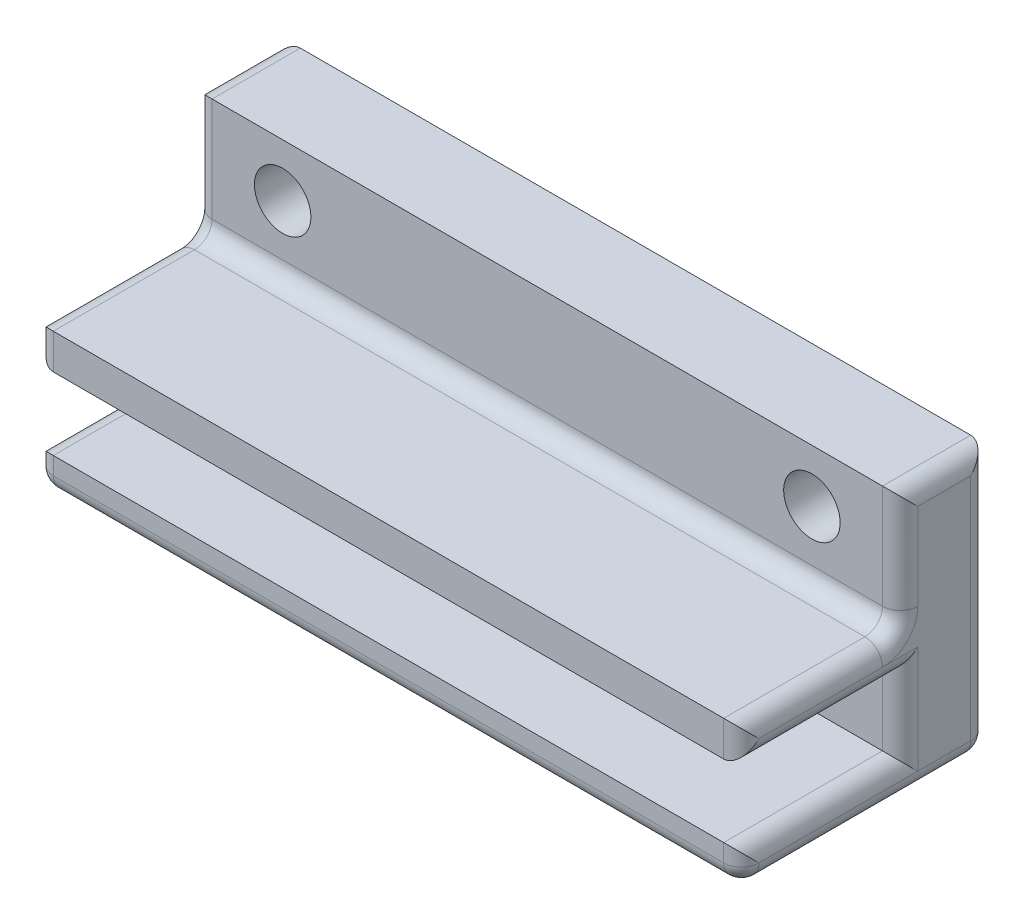
SolidWorks part; units mm, degrees
note: The reader was unsure of these and kept them because the rebuilt part matched: shared geometry of "Sketch2<3>".
material "PETG"
ref_plane "Front Plane" through (0, 0, 0) normal (0, 0, 1) x (1, 0, 0)
ref_plane "Top Plane" through (0, 0, 0) normal (0, 1, 0) x (1, 0, 0)
ref_plane "Right Plane" through (0, 0, 0) normal (1, 0, 0) x (0, 0, -1)
sketch "Sketch2" plane through (0, 0, 0) normal (0, 0, 1) x (1, 0, 0)
  line L0 (0, 7.5) -> (0, -7.5) construction
  line L1 (-20, -7.5) -> (20, -7.5)
  line L2 (-20, -7.5) -> (-20, 7.5)
  line L3 (-20, 7.5) -> (20, 7.5)
  line L4 (20, -7.5) -> (20, 7.5)
  line L5 (-20, -7.5) -> (20, 7.5) construction
  line L6 (-20, 7.5) -> (20, -7.5) construction
  line L7 (-20, 4.5) -> (20, 4.5) construction
  line L8 (-20, 0.6) -> (20, 0.6)
  line L9 (-20, -1.4) -> (20, -1.4)
  line L10 (-20, -5.5) -> (20, -5.5)
  circle A0 centre (-15, 4.5) radius 1.6
  circle A1 centre (15, 4.5) radius 1.6
  point P0 (0, 0)
  dimension "D1" = 3.2
  dimension "D2" = 30
  dimension "D3" = 40
  dimension "D4" = 3
  dimension "D5" = 15
  dimension "D6" = 4.1
  dimension "D7" = 2
  dimension "D8" = 2
extrude "Boss-Extrude1" add sketch "Sketch2" along normal blind 5 contours L2 L8 L4 L3 A0 A1 | L2 L9 L4 L8 | L2 L10 L4 L9 | L10 L2 L1 L4
extrude "Boss-Extrude2" add sketch "Sketch2<3>" along normal blind 14 contours L2 L9 L4 L8 | L10 L2 L1 L4
sketch "Sketch2<3>" plane through (0, 0, 0) normal (0, 0, 1) x (1, 0, 0) same geometry as "Sketch2"
fillet "Fillet1" radius 1 21 edges at (0, -7.5, 14) (0, -7.5, 0) (-20, 4.05, 5) (-20, 0.6, 9.5) (-20, -0.4, 14) (-20, -1.4, 9.5) (-20, -5.5, 9.5) (-20, -6.5, 14) (-20, -7.5, 7) (-20, 0, 0) (-20, 7.5, 2.5) (20, -1.4, 9.5) (20, -0.4, 14) (20, 0.6, 9.5) (20, 4.05, 5) (20, 7.5, 2.5) (20, 0, 0) (20, -7.5, 7) (20, -6.5, 14) (20, -5.5, 9.5) (0, 0.6, 5)
equation "\"DTailTube\"= 16mm'Диаметр трубки хвостового оперения"
equation "\"FusLenght\"= 700mm"
equation "\"DMotor\"= 35.2mm"
equation "\"MotorArm\"= 320mm"
equation "\"DFus\"= 150mm"
equation "\"DFusTube\"= 30mm'Диаметр трубки внутри фюзеляжа"
equation "\"FusTubeHeight\"= 40mm"
equation "\"FusCentralPartLenght\"= 410mm"
equation "\"FusNoseLenght\"= 150mm"
equation "\"WingOffset\"= 1mm'Расстояние от внутренней поверхности фюзеляжа до профиля крыла по вертикали"
equation "\"EllipseRatio\"= 0.95'Центральная часть фюзеляжа - эллипс. Этот параметр - отношение длин осей эллипса"
equation "\"FrameOffset\"= 0.6mm"
equation "\"DThreadedInsert\"= 3mm'Внешний диамер резьбовых втулок"
equation "\"ThreadedInsertLenght\"=4mm'Длина резьбовых втулок"
equation "\"ThreadedInsertThread\"=2mm'Диаметр резьбы втулки"
equation "\"CenterSectionLenght\"= 140mm'Длина центроплана"
equation "\"b\"= 1700mm'Размах"
equation "\"cwr\"= 236mm'Корневая хорда крыла"
equation "\"TR\"= 0.75'Сужение крыла"
equation "\"cwt\"= \"TR\" * \"cwr\"'Концевая хорда крыла"
equation "\"DWingMainSpar\"= 16mm'Диаметр главного лонжерона крыла"
equation "\"DWingSecondSpar\"= 8mm'Диаметр второго лонжерона крыла"
equation "\"WingSparsDistance\"= 80mm'Расстояния между отверстиями по лонжерон крыла"
equation "\"c\"= 210mm'САХ крыла"
equation "\"FusTubeLenght\"= \"FusLenght\"-50mm'Длина трубки фюзеляжа"
equation "\"bt\"=291mm'Высота лопатки хвоста"
equation "\"ct\"=182mm'Корневая хорда хвоста"
equation "\"lambda_t\"=0.3'Доля хвоста, занатая рулем высоты"
equation "\"TailTubeLenght\"=730mm'Длина хвостовой балки"
equation "\"DStringer\"=6mm'Диаметр стрингеров"
equation "\"TailConnectorBaseLenght\"=20mm'Высота основания конектора хвоста"
equation "\"CargoHolderHoleDistance\"=30mm'Расстояние между крепежными отверстиями для держателя груза"
equation "\"FuselageThickness\"=1.2mm'Толщина фюзеляжа"
equation "\"DTailSpar\"=6mm'Диаметр лонжерона хвостового оперения"
equation "\"TailSparDistance\"=40mm'Расстояние между лонжеронами хвостового оперения"
equation "\"CrossSectionWidth\"=15mm'Ширина кольцевой части шпангоута"
equation "\"HingeLenght\"=30mm'Длина отверстия под шарнир хвостового оперения"
equation "\"HingeWidth\"=2.4mm'Высота отверстия под шарнир ХО"
equation "\"HingeDepth\"=15mm'Глубина отверстия под шарнир ХО"
equation "\"DMagnet\"=3mm'Диаметр магнитов"
equation "\"MagnetHeight\"=2mm'Высота магнитов"
equation "\"PlywoodThickness\"=2.9mm'Толщина фанеры"
equation "\"D6@Sketch2\"=\"PlywoodThickness\"+1.2"
